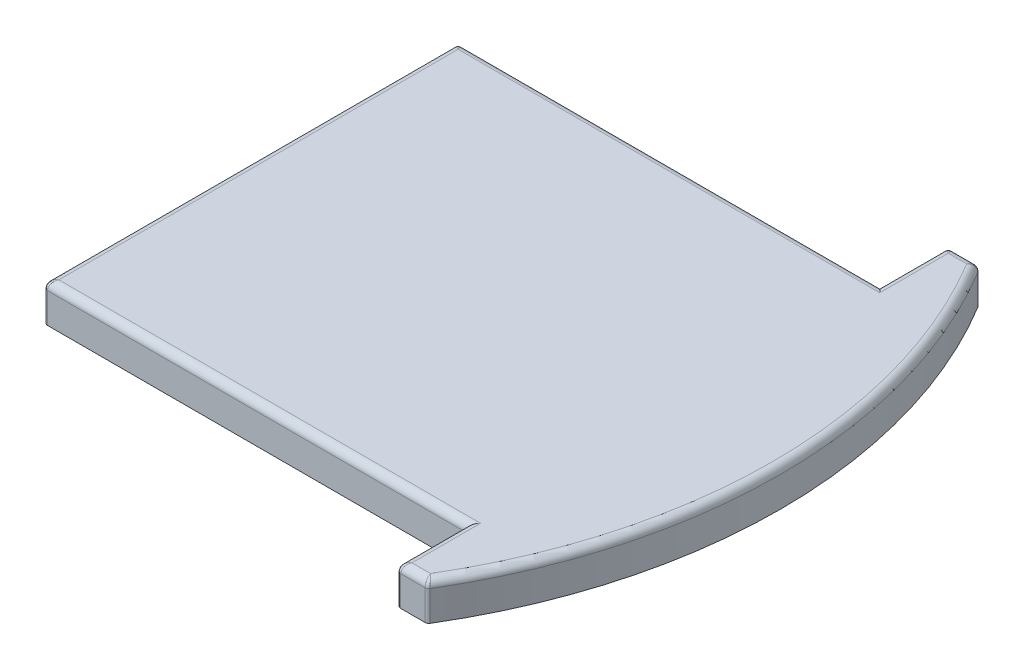
SolidWorks part; units mm, degrees
ref_plane "Front Plane" through (0, 0, 0) normal (0, 0, 1) x (1, 0, 0)
ref_plane "Top Plane" through (0, 0, 0) normal (0, 1, 0) x (1, 0, 0)
ref_plane "Right Plane" through (0, 0, 0) normal (1, 0, 0) x (0, 0, -1)
sketch "Sketch1" plane through (0, 0, 0) normal (0, 1, 0) x (1, 0, 0)
  line L1 (52.0564, -55) -> (-59.8958, -55)
  line L3 (52.0564, 55) -> (-59.8958, 55)
  line L4 (-59.8958, -55) -> (-59.8958, 55)
  line L5 (60, -50) -> (0, 0) construction
  line L6 (60, 50) -> (0, 0) construction
  line L8 (60.1042, 73.1836) -> (52.0564, 73.1836)
  line L9 (52.0564, 73.1836) -> (52.0564, 55)
  line L10 (0, 0) -> (60, 0) construction
  line L11 (52.0564, -73.1836) -> (52.0564, -55)
  line L12 (60.1042, -73.1836) -> (52.0564, -73.1836)
  arc A1 (60.1042, -73.1836) -> (60.1042, 73.1836) centre (-59.8958, 0) ccw
  point P0 (0, 0)
  dimension "D3" = 281.1109
  dimension "D1" = 120
  dimension "D2" = 110
  dimension "D4" = 52.0564
  dimension "D5" = 60
  dimension "D6" = 60.1042
  dimension "D7" = 59.8958
extrude "Boss-Extrude1" add sketch "Sketch1" along normal blind 10
fillet "Fillet1" radius 2 8 edges at (-3.9197, 10, -55) (52.0564, 10, -64.0918) (56.0803, 10, -73.1836) (80.6597, 10, 0) (56.0803, 10, 73.1836) (52.0564, 10, 64.0918) (-3.9197, 10, 55) (-59.8958, 10, 0)
fillet "Fillet2" radius 1 12 edges at (52.6422, 9.4142, -72.5978) (59.9076, 9.13, -72.8338) (-59.31, 9.4142, -54.4142) (-59.31, 9.4142, 54.4142) (59.9076, 9.13, 72.8338) (52.6422, 9.4142, 72.5978) (52.0564, 4, -73.1836) (60.1042, 4, -73.1836) (-59.8958, 4, -55) (-59.8958, 4, 55) (60.1042, 4, 73.1836) (52.0564, 4, 73.1836)
